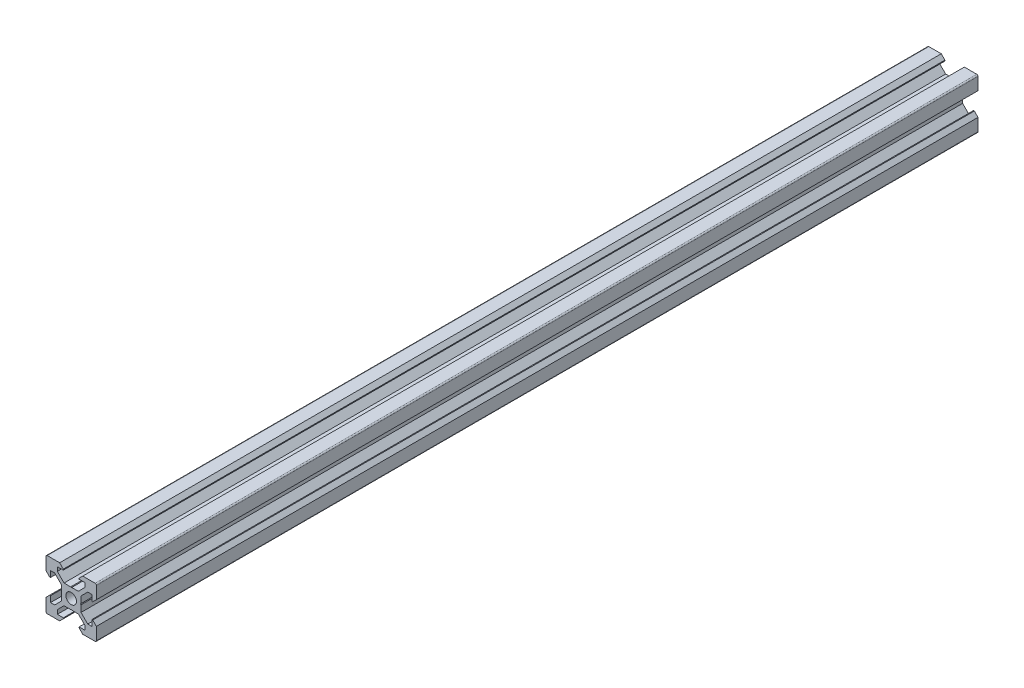
SolidWorks part; units mm, degrees
material "6061-T6 (SS)"
ref_plane "Front Plane" through (0, 0, 0) normal (0, 0, 1) x (1, 0, 0)
ref_plane "Top Plane" through (0, 0, 0) normal (0, 1, 0) x (1, 0, 0)
ref_plane "Right Plane" through (0, 0, 0) normal (1, 0, 0) x (0, 0, -1)
sketch "Sketch1" plane through (0, 0, 0) normal (0, 0, 1) x (1, 0, 0)
  line L1 (9.5, -10) -> (-9.5, -10)
  line L2 (10, -9.5) -> (10, 9.5)
  line L3 (9.5, 10) -> (-9.5, 10)
  line L4 (-10, -9.5) -> (-10, 9.5)
  line L5 (10, -10) -> (-10, 10) construction
  line L6 (10, 10) -> (-10, -10) construction
  circle A0 centre (0, 0) radius 2.1
  arc A1 (-9.5, 10) -> (-10, 9.5) centre (-9.5, 9.5) ccw
  arc A2 (10, 9.5) -> (9.5, 10) centre (9.5, 9.5) ccw
  arc A3 (9.5, -10) -> (10, -9.5) centre (9.5, -9.5) ccw
  arc A4 (-9.5, -10) -> (-10, -9.5) centre (-9.5, -9.5) cw
  point P0 (0, 0)
  line B0 (0, 0) -> (0, 10) construction
  line B1 (0, 3.69) -> (-0.21, 3.9)
  line B2 (-0.21, 3.9) -> (-2.8393, 3.9)
  line B3 (-2.8393, 3.9) -> (-5.5, 6.5607)
  line B4 (-5.5, 6.5607) -> (-5.5, 8.2)
  line B5 (-5.5, 8.2) -> (-3.125, 8.2)
  line B6 (-3.125, 8.2) -> (-3.125, 8.545)
  line B7 (-3.125, 8.545) -> (-4.58, 10)
  line B8 (-4.58, 10) -> (4.58, 10)
  line B9 (0, 0) -> (-5.9132, 5.9132) construction
  line B10 (3.125, 8.545) -> (4.58, 10)
  line B11 (3.125, 8.2) -> (3.125, 8.545)
  line B12 (5.5, 8.2) -> (3.125, 8.2)
  line B13 (5.5, 6.5607) -> (5.5, 8.2)
  line B14 (2.8393, 3.9) -> (5.5, 6.5607)
  line B15 (0.21, 3.9) -> (2.8393, 3.9)
  line B16 (0, 3.69) -> (0.21, 3.9)
  line B17 (0, 0) -> (-10, 0) construction
  line B18 (-3.69, 0) -> (-3.9, -0.21)
  line B19 (-3.9, -0.21) -> (-3.9, -2.8393)
  line B20 (-3.9, -2.8393) -> (-6.5607, -5.5)
  line B21 (-6.5607, -5.5) -> (-8.2, -5.5)
  line B22 (-8.2, -5.5) -> (-8.2, -3.125)
  line B23 (-8.2, -3.125) -> (-8.545, -3.125)
  line B24 (-8.545, -3.125) -> (-10, -4.58)
  line B25 (-10, -4.58) -> (-10, 4.58)
  line B26 (0, 0) -> (-5.9132, -5.9132) construction
  line B27 (-8.545, 3.125) -> (-10, 4.58)
  line B28 (-8.2, 3.125) -> (-8.545, 3.125)
  line B29 (-8.2, 5.5) -> (-8.2, 3.125)
  line B30 (-6.5607, 5.5) -> (-8.2, 5.5)
  line B31 (-3.9, 2.8393) -> (-6.5607, 5.5)
  line B32 (-3.9, 0.21) -> (-3.9, 2.8393)
  line B33 (-3.69, 0) -> (-3.9, 0.21)
  line B34 (0, 0) -> (0, -10) construction
  line B35 (0, -3.69) -> (0.21, -3.9)
  line B36 (0.21, -3.9) -> (2.8393, -3.9)
  line B37 (2.8393, -3.9) -> (5.5, -6.5607)
  line B38 (5.5, -6.5607) -> (5.5, -8.2)
  line B39 (5.5, -8.2) -> (3.125, -8.2)
  line B40 (3.125, -8.2) -> (3.125, -8.545)
  line B41 (3.125, -8.545) -> (4.58, -10)
  line B42 (4.58, -10) -> (-4.58, -10)
  line B43 (0, 0) -> (5.9132, -5.9132) construction
  line B44 (-3.125, -8.545) -> (-4.58, -10)
  line B45 (-3.125, -8.2) -> (-3.125, -8.545)
  line B46 (-5.5, -8.2) -> (-3.125, -8.2)
  line B47 (-5.5, -6.5607) -> (-5.5, -8.2)
  line B48 (-2.8393, -3.9) -> (-5.5, -6.5607)
  line B49 (-0.21, -3.9) -> (-2.8393, -3.9)
  line B50 (0, -3.69) -> (-0.21, -3.9)
  line B51 (0, 0) -> (10, 0) construction
  line B52 (3.69, 0) -> (3.9, 0.21)
  line B53 (3.9, 0.21) -> (3.9, 2.8393)
  line B54 (3.9, 2.8393) -> (6.5607, 5.5)
  line B55 (6.5607, 5.5) -> (8.2, 5.5)
  line B56 (8.2, 5.5) -> (8.2, 3.125)
  line B57 (8.2, 3.125) -> (8.545, 3.125)
  line B58 (8.545, 3.125) -> (10, 4.58)
  line B59 (10, 4.58) -> (10, -4.58)
  line B60 (0, 0) -> (5.9132, 5.9132) construction
  line B61 (8.545, -3.125) -> (10, -4.58)
  line B62 (8.2, -3.125) -> (8.545, -3.125)
  line B63 (8.2, -5.5) -> (8.2, -3.125)
  line B64 (6.5607, -5.5) -> (8.2, -5.5)
  line B65 (3.9, -2.8393) -> (6.5607, -5.5)
  line B66 (3.9, -0.21) -> (3.9, -2.8393)
  line B67 (3.69, 0) -> (3.9, -0.21)
  dimension "D1" = 4.2
  dimension "D3" = 0.5
  dimension "D2" = 20
sketch_block_instance "V Slot 1-4"
sketch_block "V Slot 1" parameters "D1"=10, "D2"=11, "D3"=4.3, "D4"=1.8, "D5"=0.21, "D6"=45, "D7"=9.16, "D8"=1.5, "D9"=6.25
sketch_block_instance "V Slot 1-5"
sketch_block_instance "V Slot 1-6"
sketch_block_instance "V Slot 1-7"
extrude "Boss-Extrude1" add sketch "Sketch1" along normal blind 350 contours B67 B52 B53 B54 B55 B56 B57 B58 L2 A2 L3 B10 B11 B12 B13 B14 B15 B16 B1 B2 B3 B4 B5 B6 B7 A1 L4 B27 B28 B29 B30 B31 B32 B33 B18 B19 B20 B21 B22 B23 B24 A4 L1 B44 B45 B46 B47 B48 B49 region at (7.04, -9.7172, 0)
